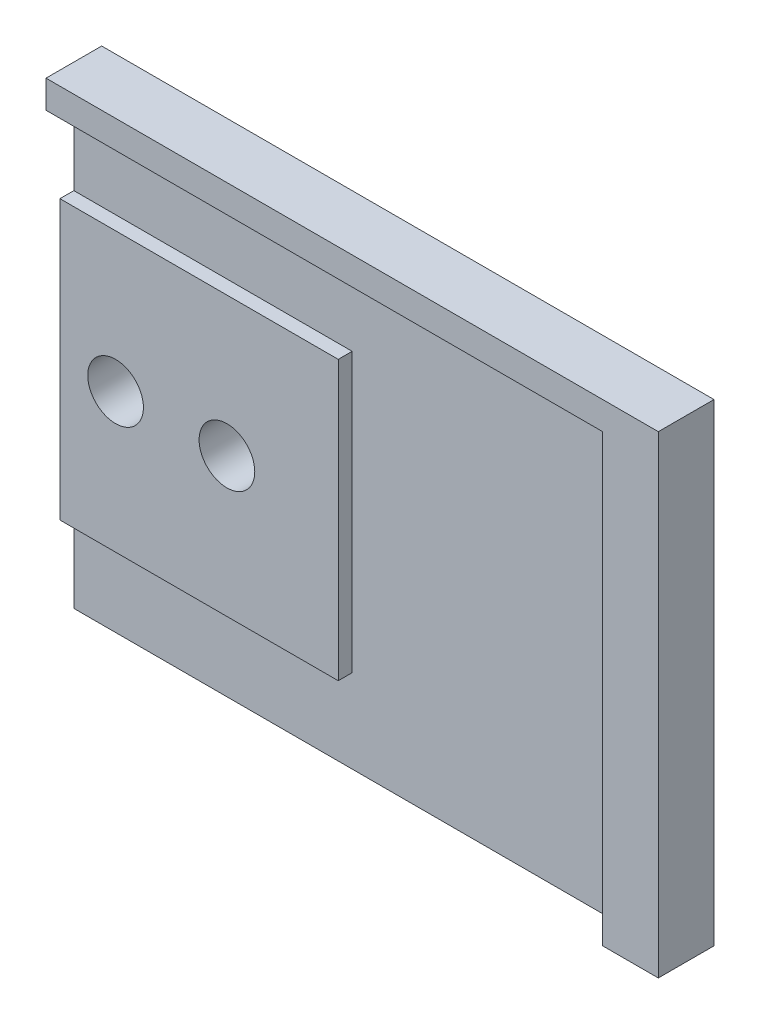
SolidWorks part; units mm, degrees
ref_plane "Ebene vorne" through (0, 0, 0) normal (0, 0, 1) x (1, 0, 0)
ref_plane "Ebene oben" through (0, 0, 0) normal (0, 1, 0) x (1, 0, 0)
ref_plane "Ebene rechts" through (0, 0, 0) normal (1, 0, 0) x (0, 0, -1)
sketch "Skizze1" plane through (0, 0, 0) normal (0, 0, 1) x (1, 0, 0)
  line L1 (-46.2861, 20.7994) -> (63.7139, 20.7994)
  line L2 (-46.2861, 20.7994) -> (-46.2861, -64.2006)
  line L3 (-46.2861, -64.2006) -> (63.7139, -64.2006)
  line L4 (63.7139, 20.7994) -> (63.7139, -64.2006)
  dimension "D1" = 110
  dimension "D2" = 85
extrude "Aufsatz-Linear austragen1" add sketch "Skizze1" along normal blind 10
sketch "Skizze2" plane through (0, 0, 10) normal (0, 0, 1) x (1, 0, 0)
  line L0 (-46.2861, 20.7994) -> (-46.2861, -64.2006) construction
  line L1 (-46.2861, 15.7994) -> (53.7139, 15.7994)
  line L2 (-46.2861, 15.7994) -> (-46.2861, -64.2006)
  line L3 (-46.2861, -64.2006) -> (53.7139, -64.2006)
  line L4 (53.7139, 15.7994) -> (53.7139, -64.2006)
  line L5 (-46.2861, -64.2006) -> (63.7139, -64.2006) construction
  dimension "D1" = 100
  dimension "D2" = 80
extrude "Schnitt-Linear austragen1" cut sketch "Skizze2" against normal blind 5
sketch "Skizze3" plane through (0, 0, 5) normal (0, 0, 1) x (1, 0, 0)
  line L0 (-46.2861, 15.7994) -> (-46.2861, -64.2006) construction
  line L1 (-46.2861, 0.7994) -> (3.7139, 0.7994)
  line L2 (-46.2861, 0.7994) -> (-46.2861, -49.2006)
  line L3 (-46.2861, -49.2006) -> (3.7139, -49.2006)
  line L4 (3.7139, 0.7994) -> (3.7139, -49.2006)
  line L5 (-46.2861, -64.2006) -> (53.7139, -64.2006) construction
  dimension "D1" = 50
  dimension "D2" = 50
  dimension "D3" = 15
extrude "Aufsatz-Linear austragen2" add sketch "Skizze3" along normal blind 2.5
sketch "Skizze4" plane through (0, 0, 7.5) normal (0, 0, 1) x (1, 0, 0)
  line L0 (-46.2861, 0.7994) -> (-46.2861, -49.2006) construction
  circle A0 centre (-36.2861, -24.2006) radius 5
  circle A1 centre (-16.2861, -24.2006) radius 5
  dimension "D1" = 10
  dimension "D2" = 20
extrude "Schnitt-Linear austragen2" cut sketch "Skizze4" against normal blind 22.5
